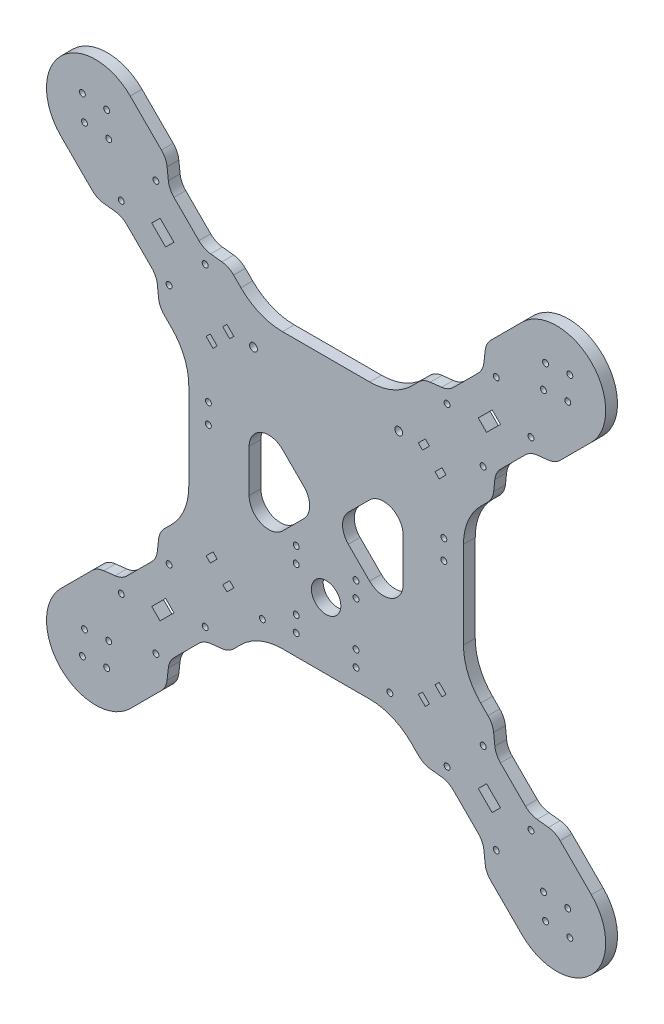
SolidWorks part; units mm, degrees
ref_plane "Front Plane" through (0, 0, 0) normal (0, 0, 1) x (1, 0, 0)
ref_plane "Top Plane" through (0, 0, 0) normal (0, 1, 0) x (1, 0, 0)
ref_plane "Right Plane" through (0, 0, 0) normal (1, 0, 0) x (0, 0, -1)
sketch "Sketch4" plane through (0, 0, 0) normal (0, 0, 1) x (1, 0, 0)
  line L0 (-117.5, 117.5) -> (117.5, -117.5) construction
  line L1 (-117.5, -117.5) -> (117.5, 117.5) construction
  line L2 (-1000, 0) -> (49000, 0) construction
  line L3 (0, -1000) -> (0, 49000) construction
  line L4 (-70, -34.6447) -> (-70, 34.6447)
  line L5 (34.6447, 70) -> (-34.6447, 70)
  line L6 (-70, 34.6447) -> (-135.1777, 99.8223)
  line L7 (-34.6447, 70) -> (-99.8223, 135.1777)
  line L8 (-135.1777, 99.8223) -> (-99.8223, 135.1777) construction
  line L9 (70, -34.6447) -> (70, 34.6447)
  line L10 (70, 34.6447) -> (135.1777, 99.8223)
  line L11 (34.6447, 70) -> (99.8223, 135.1777)
  line L12 (70, -34.6447) -> (135.1777, -99.8223)
  line L13 (34.6447, -70) -> (99.8223, -135.1777)
  line L14 (34.6447, -70) -> (-34.6447, -70)
  line L15 (-34.6447, -70) -> (-99.8223, -135.1777)
  line L16 (-70, -34.6447) -> (-135.1777, -99.8223)
  line L17 (-124.5711, 89.2157) -> (-89.2157, 124.5711) construction
  line L18 (-120.3284, 84.9731) -> (-84.9731, 120.3284) construction
  arc A0 (-135.1777, 99.8223) -> (-99.8223, 135.1777) centre (-117.5, 117.5) cw
  arc A1 (135.1777, 99.8223) -> (99.8223, 135.1777) centre (117.5, 117.5) ccw
  arc A2 (135.1777, -99.8223) -> (99.8223, -135.1777) centre (117.5, -117.5) cw
  arc A3 (-135.1777, -99.8223) -> (-99.8223, -135.1777) centre (-117.5, -117.5) ccw
  point P13 (-117.5, 117.5)
  point P17 (-135.1777, 135.1777)
  point P19 (0, 70)
  point P24 (70, 0)
  point P31 (-70, 0)
  dimension "D6" = 40
  dimension "D1" = 235
  dimension "D2" = 235
  dimension "D3" = 70
  dimension "D4" = 70
  dimension "D5" = 50
  dimension "D7" = 6
extrude "Boss-Extrude1" add sketch "Sketch4" along normal blind 6
fillet "Fillet1" radius 30 8 edges at (34.6447, -70, 3) (70, -34.6447, 3) (70, 34.6447, 3) (34.6447, 70, 3) (-34.6447, 70, 3) (-70, 34.6447, 3) (-70, -34.6447, 3) (-34.6447, -70, 3)
sketch "Sketch8" plane through (0, 0, 6) normal (0, 0, 1) x (1, 0, 0)
  line L0 (-120.3284, 84.9731) -> (-84.9731, 120.3284) construction
  line L1 (-117.5, 117.5) -> (117.5, -117.5) construction
  line L2 (-88.8622, 84.6195) -> (-84.6195, 88.8622)
  line L3 (-88.8622, 84.6195) -> (-81.7911, 77.5485)
  line L4 (-84.6195, 88.8622) -> (-77.5485, 81.7911)
  line L5 (-81.7911, 77.5485) -> (-77.5485, 81.7911)
  circle A0 centre (-104.4185, 86.7409) radius 1.5
  circle A2 centre (-80.0233, 61.6386) radius 1.5
  circle A4 centre (-86.7409, 104.4185) radius 1.5
  circle A5 centre (-61.6386, 80.0233) radius 1.5
  dimension "D1" = 3
  dimension "D2" = 10
  dimension "D3" = 12.5
  dimension "D4" = 13
  dimension "D5" = 45
  dimension "D6" = 10
  dimension "D7" = 12.5
  dimension "D8" = 45
  dimension "D9" = 13
  dimension "D10" = 6
  dimension "D11" = 3
  dimension "D12" = 22.5
  dimension "D13" = 10
sketch "Sketch9" plane through (0, 0, 6) normal (0, 0, 1) x (1, 0, 0)
  line L0 (-135.1777, 99.8223) -> (-99.8223, 135.1777) construction
  line L1 (-117.5, 117.5) -> (117.5, -117.5) construction
  circle A0 centre (-124.2175, 124.2175) radius 1.5
  circle A1 centre (-110.7825, 110.7825) radius 1.5
  circle A2 centre (-123.1569, 111.8431) radius 1.5
  circle A3 centre (-111.8431, 123.1569) radius 1.5
  dimension "D5" = 3
  dimension "D1" = 8
  dimension "D2" = 8
  dimension "D3" = 9.5
  dimension "D4" = 9.5
extrude "Cut-Extrude1" cut sketch "Sketch8" against normal through all both and the other way through all
extrude "Cut-Extrude2" cut sketch "Sketch9" against normal through all both and the other way through all
mirror "Mirror1" about plane through (0, 0, 0) normal (1, 0, 0) of "Cut-Extrude2", "Cut-Extrude1"
mirror "Mirror2" about plane through (0, 0, 0) normal (0, 1, 0) of "Mirror1"
sketch "Sketch10" plane through (0, 0, 6) normal (0, 0, 1) x (1, 0, 0)
  line L0 (-70, -34.6447) -> (-70, 34.6447) construction
  line L1 (70, -34.6447) -> (70, 34.6447) construction
  line L2 (34.6447, 70) -> (-34.6447, 70) construction
  line L3 (-49.1421, -53.3848) -> (-47.0208, -55.5061)
  line L4 (0, -201000) -> (0, 249000) construction
  line L5 (-201000, 0) -> (249000, 0) construction
  line L6 (-4.2426, 0) -> (-39.2426, 35)
  line L7 (-39.2426, 35) -> (-39.2426, -35)
  line L8 (-39.2426, -35) -> (-4.2426, 0)
  line L9 (-117.5, 117.5) -> (117.5, -117.5) construction
  line L10 (-117.5, -117.5) -> (117.5, 117.5) construction
  line L11 (0, -3.3) -> (0, 3.3) construction
  line L12 (39.2426, 35) -> (39.2426, -35)
  line L13 (4.2426, 0) -> (39.2426, 35)
  line L14 (39.2426, -35) -> (4.2426, 0)
  line L21 (3.3, 0) -> (-3.3, 0) construction
  line L22 (-57.6274, -44.8995) -> (-55.5061, -47.0208)
  line L23 (-59.0416, -50.5563) -> (-55.5061, -47.0208)
  line L24 (-61.163, -48.435) -> (-59.0416, -50.5563)
  line L25 (-61.163, 48.435) -> (-59.0416, 50.5563)
  line L26 (-61.163, 48.435) -> (-57.6274, 44.8995)
  line L27 (-57.6274, 44.8995) -> (-55.5061, 47.0208)
  line L28 (-59.0416, 50.5563) -> (-55.5061, 47.0208)
  line L29 (-61.163, -48.435) -> (-57.6274, -44.8995)
  line L30 (57.6274, 44.8995) -> (55.5061, 47.0208)
  line L31 (59.0416, 50.5563) -> (55.5061, 47.0208)
  line L32 (61.163, 48.435) -> (59.0416, 50.5563)
  line L33 (61.163, 48.435) -> (57.6274, 44.8995)
  line L34 (61.163, -48.435) -> (57.6274, -44.8995)
  line L35 (61.163, -48.435) -> (59.0416, -50.5563)
  line L36 (59.0416, -50.5563) -> (55.5061, -47.0208)
  line L37 (57.6274, -44.8995) -> (55.5061, -47.0208)
  line L38 (-52.6777, 56.9203) -> (-50.5563, 59.0416)
  line L39 (-52.6777, 56.9203) -> (-49.1421, 53.3848)
  line L40 (-49.1421, 53.3848) -> (-47.0208, 55.5061)
  line L41 (-50.5563, 59.0416) -> (-47.0208, 55.5061)
  line L42 (-50.5563, -59.0416) -> (-47.0208, -55.5061)
  line L43 (-52.6777, -56.9203) -> (-50.5563, -59.0416)
  line L44 (-52.6777, -56.9203) -> (-49.1421, -53.3848)
  line L45 (52.6777, -56.9203) -> (49.1421, -53.3848)
  line L46 (52.6777, -56.9203) -> (50.5563, -59.0416)
  line L47 (50.5563, -59.0416) -> (47.0208, -55.5061)
  line L48 (49.1421, -53.3848) -> (47.0208, -55.5061)
  line L49 (49.1421, 53.3848) -> (47.0208, 55.5061)
  line L50 (50.5563, 59.0416) -> (47.0208, 55.5061)
  line L51 (52.6777, 56.9203) -> (50.5563, 59.0416)
  line L52 (52.6777, 56.9203) -> (49.1421, 53.3848)
  line L53 (-15.25, -21) -> (15.25, -51.5) construction
  line L54 (-22.2183, -70) -> (22.2183, -70) construction
  circle A0 centre (-60, 20) radius 1.5
  circle A1 centre (-60, 10) radius 1.5
  circle A2 centre (60, 20) radius 1.5
  circle A3 centre (60, 10) radius 1.5
  circle A4 centre (-15.25, -21) radius 1.5
  circle A5 centre (15.25, -21) radius 1.5
  circle A6 centre (-15.25, -51.5) radius 1.5
  circle A7 centre (15.25, -51.5) radius 1.5
  circle A8 centre (0, -36.25) radius 7.5
  circle A11 centre (32.5, -62) radius 1.5
  circle A12 centre (-32.5, -62) radius 1.5
  circle A13 centre (15.25, -29) radius 1.5
  circle A14 centre (-15.25, -29) radius 1.5
  circle A15 centre (15.25, -59.5) radius 1.5
  circle A16 centre (-15.25, -59.5) radius 1.5
  circle A19 centre (-37, 55.7426) radius 2
  circle A20 centre (37, 55.7426) radius 2
  dimension "D2" = 10
  dimension "D5" = 3
  dimension "D8" = 3
  dimension "D17" = 15
  dimension "D18" = 3
  dimension "D19" = 3
  dimension "D25" = 4
  dimension "D26" = 4
  dimension "D1" = 10
  dimension "D3" = 10
  dimension "D4" = 50
  dimension "D6" = 30.5
  dimension "D7" = 30.5
  dimension "D9" = 15.25
  dimension "D10" = 21
  dimension "D11" = 3
  dimension "30" = 35
  dimension "D12" = 6
  dimension "D13" = 3
  dimension "D14" = 5
  dimension "D15" = 20
  dimension "D16" = 3
  dimension "D20" = 8
  dimension "D21" = 65
  dimension "D22" = 32.5
  dimension "D24" = 8
  dimension "D23" = 2
extrude "Cut-Extrude3" cut sketch "Sketch10" against normal through all both and the other way through all
fillet "Fillet2" radius 10 6 edges at (4.2426, 0, 3) (39.2426, -35, 3) (39.2426, 35, 3) (-39.2426, -35, 3) (-39.2426, 35, 3) (-4.2426, 0, 3)
sketch "Sketch11" plane through (0, 0, 6) normal (0, 0, 1) x (1, 0, 0)
  line L1 (-34.6447, 70) -> (-99.8223, 135.1777) construction
  line L2 (-80.0233, 104.065) -> (-62.3457, 86.3873)
  line L3 (-62.3457, 86.3873) -> (-49.6177, 84.9731)
  line L4 (-49.6177, 84.9731) -> (-81.4376, 116.7929)
  line L5 (-81.4376, 116.7929) -> (-80.0233, 104.065)
  line L6 (-80.0233, 104.065) -> (-74.3665, 109.7218) construction
  line L7 (-62.3457, 86.3873) -> (-56.6888, 92.0442) construction
  line L8 (-120.3284, 84.9731) -> (-84.9731, 120.3284) construction
  dimension "D1" = 45
  dimension "D2" = 8
  dimension "D3" = 10
  dimension "D4" = 10
  dimension "D5" = 5
extrude "Cut-Extrude4" cut sketch "Sketch11" against normal through all both and the other way through all
ref_plane "Plane1" through (0, 0, 0) normal (0.7071, 0.7071, 0) x (0.7071, -0.7071, 0)
mirror "Mirror4" about plane through (0, 0, 0) normal (0.7071, 0.7071, 0) of "Cut-Extrude4"
ref_axis "Axis1" through (0, 0, 0) along (0, 0, 1)
pattern_circular "CirPattern2" count 4 over 360 about axis through (0, 0, 0) along (0, 0, 1) of "Cut-Extrude4", "Mirror4"
fillet "Fillet3" radius 10 32 edges at (-49.6177, 84.9731, 3) (-62.3457, 86.3873, 3) (-80.0233, 104.065, 3) (-81.4376, 116.7929, 3) (116.7929, 81.4376, 3) (104.065, 80.0233, 3) (86.3873, 62.3457, 3) (84.9731, 49.6177, 3) (80.0233, 104.065, 3) (81.4376, 116.7929, 3) (62.3457, 86.3873, 3) (49.6177, 84.9731, 3) (116.7929, -81.4376, 3) (104.065, -80.0233, 3) (86.3873, -62.3457, 3) (84.9731, -49.6177, 3) (81.4376, -116.7929, 3) (80.0233, -104.065, 3) (62.3457, -86.3873, 3) (49.6177, -84.9731, 3) (-49.6177, -84.9731, 3) (-62.3457, -86.3873, 3) (-80.0233, -104.065, 3) (-81.4376, -116.7929, 3) (-116.7929, -81.4376, 3) (-104.065, -80.0233, 3) (-86.3873, -62.3457, 3) (-84.9731, -49.6177, 3) (-84.9731, 49.6177, 3) (-86.3873, 62.3457, 3) (-104.065, 80.0233, 3) (-116.7929, 81.4376, 3)
sketch "Sketch12" plane through (0, 0, 0) normal (0, 0, 1) x (1, 0, 0)
  line L0 (117.5, 117.5) -> (-117.5, -117.5) construction
  line L1 (-117.5, 117.5) -> (117.5, -117.5) construction
sketch "Sketch14" plane through (0, 0, 6) normal (0, 0, 1) x (1, 0, 0)
  line L6 (-15.25, -29) -> (15.25, -59.5) construction
  line L7 (-15.25, -59.5) -> (15.25, -29) construction
  line L13 (-17.25, -27) -> (17.25, -27) construction
  line L14 (-17.25, -27) -> (-17.25, -61.5) construction
  line L15 (-17.25, -61.5) -> (17.25, -61.5) construction
  line L16 (17.25, -27) -> (17.25, -61.5) construction
  line L17 (-17.25, -27) -> (17.25, -61.5) construction
  line L18 (-17.25, -61.5) -> (17.25, -27) construction
  point P4 (0, -44.25)
  point P5 (0, -44.25)
  dimension "D1" = 34.5
equation "\"D6@Sketch8\"=\"D2@Sketch8\""
equation "\"D7@Sketch8\"=\"D3@Sketch8\""
equation "\"D8@Sketch8\"=\"D5@Sketch8\""
equation "\"D9@Sketch8\"=\"D4@Sketch8\""
equation "\"D2@Sketch9\"=\"D1@Sketch9\""
equation "\"D4@Sketch9\"=\"D3@Sketch9\""
equation "\"D9@Sketch10\"=\"D6@Sketch10\"/2"
equation "\"D22@Sketch10\"= \"D21@Sketch10\" / 2"
